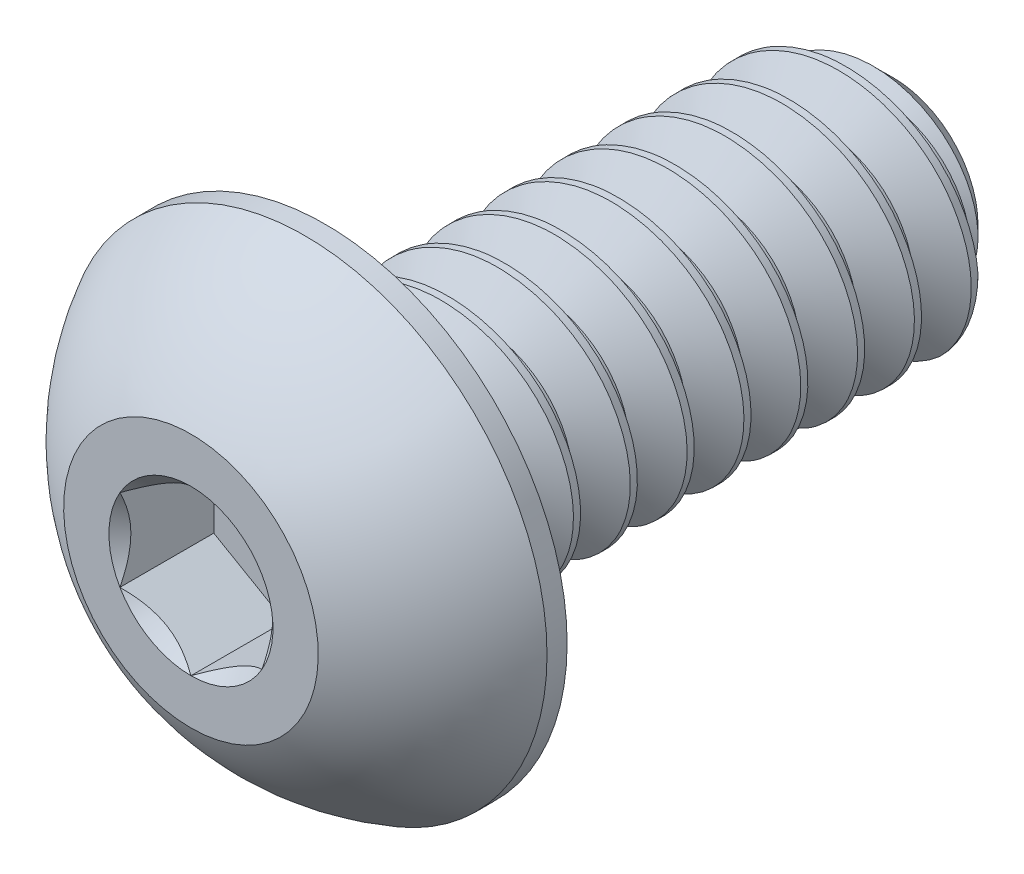
SolidWorks part; units mm, degrees
ref_plane "Front" through (0, 0, 0) normal (0, 0, 1) x (1, 0, 0)
ref_plane "Top" through (0, 0, 0) normal (0, 1, 0) x (1, 0, 0)
ref_plane "Right" through (0, 0, 0) normal (1, 0, 0) x (0, 0, -1)
sketch "Sketch1" plane through (0, 0, 0) normal (1, 0, 0) x (0, 0, -1)
  line L2 (1.4986, 1.4224) -> (7.8486, 1.4224)
  line L3 (7.8486, 1.4224) -> (7.8486, 0)
  line L4 (7.8486, 0) -> (1.4986, 0)
  line L6 (1.2738, 2.7051) -> (1.4986, 2.7051) construction
  line L7 (7.8486, 1.4224) -> (7.8486, -1.4224) construction
  line L8 (0, 0) -> (1.4986, 0) construction
  line L9 (1.4986, 2.7051) -> (1.4986, -2.7051) construction
  line L11 (1.4986, 1.4224) -> (1.4986, 0)
  line L13 (0, 0.7937) -> (0, -0.7937) construction
  line L14 (0, 0.7937) -> (0, 1.4224) construction
  arc A3 (0, 1.4224) -> (1.2738, 2.7051) centre (2.7151, 0) cw construction
  dimension "D1" = 0.2248
revolve "Revolve1" add sketch "Sketch1" angle 360 mid plane about L4
sketch "Sketch3" plane through (0, 0, -7.8486) normal (0, 0, -1) x (-1, 0, 0)
  circle A0 centre (0, 0) radius 1.4224
curve "Helix/Spiral1" pitch 0.635 height 6.985 radius 1.4224 centre (0, 0, -7.8486) axis (0, 0, 1) start towards (0, 1, 0)
sketch "Sketch2" plane through (0, 0, 0) normal (1, 0, 0) x (0, 0, -1)
  line L0 (7.8486, 1.4224) -> (8.4042, 1.4224)
  line L1 (8.4042, 1.4224) -> (8.1661, 1.01)
  line L2 (8.1661, 1.01) -> (8.0867, 1.01)
  line L3 (8.0867, 1.01) -> (7.8486, 1.4224)
  line L4 (7.9677, 1.2162) -> (8.2852, 1.2162) construction
  dimension "D1" = 60
  dimension "D2" = 0.0794
  dimension "D3" = 0.3175
chamfer "Chamfer1" distance 0.4763 angle 45 1 edges at (0, 1.4224, -7.8486)
sweep "Cut-Sweep1" cut profiles "Sketch2" path "Helix/Spiral1" align with end faces yes
sketch "Sketch7" plane through (0, 0, 0) normal (1, 0, 0) x (0, 0, -1)
  line L6 (1.2738, 2.7051) -> (1.4986, 2.7051) construction
  line L8 (0, 0) -> (1.4986, 0) construction
  line L11 (1.4986, 2.7051) -> (1.4986, -2.7051) construction
  line L12 (1.2738, 2.7051) -> (1.4986, 2.7051)
  line L13 (0, 0) -> (1.4986, 0)
  line L14 (0, 0.7937) -> (0, -0.7937) construction
  line L15 (1.4986, 2.7051) -> (1.4986, 0)
  line L16 (0, 1.4224) -> (0, 0)
  arc A2 (1.2738, 2.7051) -> (0, 1.4224) centre (2.7151, 0) ccw construction
  arc A3 (1.2738, 2.7051) -> (0, 1.4224) centre (2.7151, 0) ccw
revolve "Revolve2" add sketch "Sketch7" angle 360 mid plane about L13
sketch "Sketch5" plane through (0, 0, 0) normal (0, 0, 1) x (1, 0, 0)
  line L1 (0.7937, -0.4583) -> (0.7937, 0.4583)
  line L2 (0.7937, 0.4583) -> (0, 0.9165)
  line L3 (0, 0.9165) -> (-0.7937, 0.4583)
  line L4 (-0.7937, 0.4583) -> (-0.7937, -0.4583)
  line L5 (-0.7937, -0.4583) -> (0, -0.9165)
  line L6 (0, -0.9165) -> (0.7937, -0.4583)
  circle A0 centre (0, 0) radius 0.7937 construction
extrude "Cut-Extrude2" cut sketch "Sketch5" against normal blind 1.049
sketch "Sketch6" plane through (0, 0, 0) normal (0, 0, 1) x (1, 0, 0)
  circle A0 centre (0, 0) radius 0.9165
extrude "Cut-Extrude3" cut sketch "Sketch6" against normal blind 1.049 draft 45
sketch "Sketch9" [suppressed] plane through (0, 0, -1.4986) normal (0, 0, 1) x (1, 0, 0)
  circle A2 centre (0, 0) radius 1.4224
extrude "Boss-Extrude2" [suppressed] add sketch "Sketch9" against normal offset from surface (12.7 mm away) 31.75 up to face at (0, 0.9462, -7.8486)
equation "\"D3@Helix/Spiral1\" = \"Lg@Sketch1\" + \"D4@Helix/Spiral1\""
equation "\"D2@Sketch2\" = \"D4@Helix/Spiral1\" * .125"
equation "\"D3@Sketch2\" = \"D4@Helix/Spiral1\" * .5"
equation "\"D1@Chamfer1\" = \"D4@Helix/Spiral1\" * .75"
equation "\"D1@Cut-Extrude2\" = \"Head Ht@Sketch1\" * .7"
equation "\"D1@Sketch1\" = \"Head Ht@Sketch1\" * .15"
equation "\"D1@Cut-Extrude3\" = \"D1@Cut-Extrude2\""
